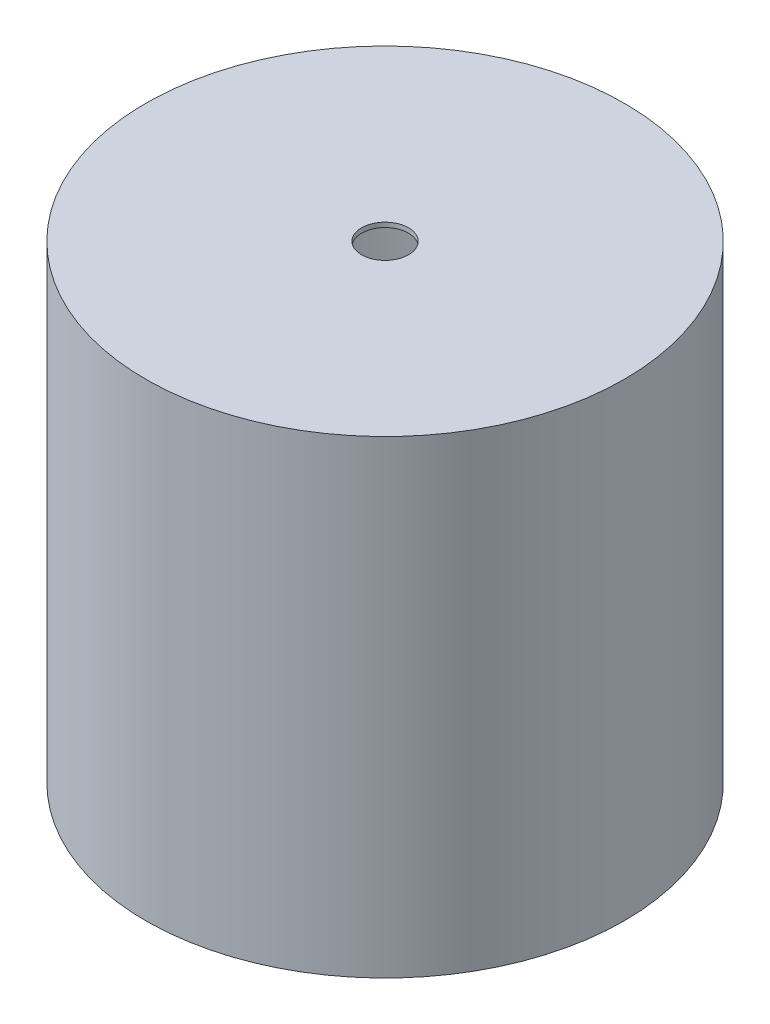
SolidWorks part; units mm, degrees
ref_plane "Front" through (0, 0, 0) normal (0, 0, 1) x (1, 0, 0)
ref_plane "Top" through (0, 0, 0) normal (0, 1, 0) x (1, 0, 0)
ref_plane "Right" through (0, 0, 0) normal (1, 0, 0) x (0, 0, -1)
sketch "Sketch1" plane through (0, 0, 0) normal (0, 1, 0) x (1, 0, 0)
  circle A0 centre (0, 0) radius 50
  dimension "D1" = 100
extrude "Extrude-Thin1" add sketch "Sketch1" along normal blind 100 thin thin type one direction wall 1
extrude "Boss-Extrude1" add sketch "Sketch1<2>" along normal blind 1
sketch "Sketch1<2>" plane through (0, 0, 0) normal (0, 1, 0) x (1, 0, 0) same geometry as "Sketch1"
pattern_linear "LPattern1" count 2 spacing 99 along (0, 1, 0) of "Boss-Extrude1"
sketch "Sketch3" plane through (0, 0, 0) normal (0, -1, 0) x (1, 0, 0)
  circle A0 centre (0, 0) radius 5
  dimension "D1" = 10
extrude "Cut-Extrude1" cut sketch "Sketch3" against normal through all
